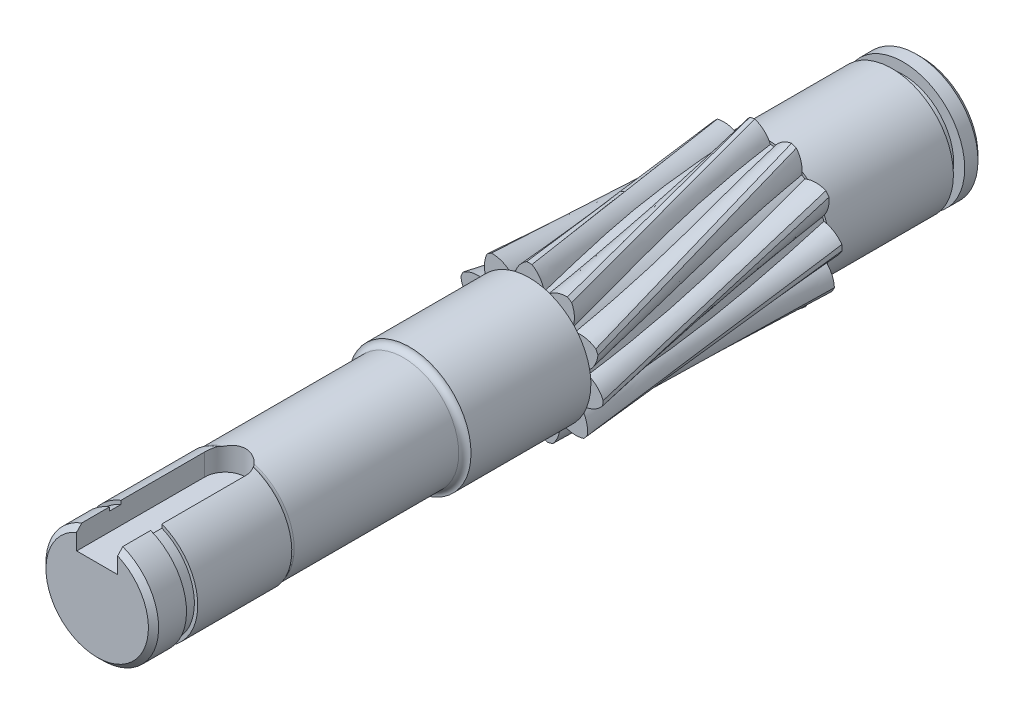
SolidWorks part; units mm, degrees
ref_plane "Plan de face" through (0, 0, 0) normal (0, 0, 1) x (1, 0, 0)
ref_plane "Plan de dessus" through (0, 0, 0) normal (0, 1, 0) x (1, 0, 0)
ref_plane "Plan de droite" through (0, 0, 0) normal (1, 0, 0) x (0, 0, -1)
sketch "Esquisse5" plane through (0, 0, 0) normal (0, 0, 1) x (1, 0, 0)
  circle A0 centre (0, 0) radius 5.75
  dimension "D1" = 11.5
extrude "Extrusion1" add sketch "Esquisse5" against normal blind 23.3
sketch "Esquisse1" plane through (0, 0, 0) normal (0, 0, 1) x (1, 0, 0)
  line L0 (0, 8.3971) -> (0, -8.0185) construction
  line L1 (-0.25, 7.2457) -> (0, 0) construction
  line L2 (0, 0) -> (0.25, 7.2457) construction
  line L3 (1.45, 5.5642) -> (0, 0) construction
  line L4 (0, 0) -> (-1.45, 5.5642) construction
  circle A0 centre (0, 0) radius 5.75 construction
  circle A1 centre (0, 0) radius 7.25 construction
  arc A2 (-0.25, 7.2457) -> (0.25, 7.2457) centre (0, 0) cw
  arc A3 (-1.45, 5.5642) -> (1.45, 5.5642) centre (0, 0) cw
  arc A4 (-1.45, 5.5642) -> (-0.25, 7.2457) centre (1.1069, 5.0084) cw
  arc A5 (1.45, 5.5642) -> (0.25, 7.2457) centre (-1.1069, 5.0084) ccw
  circle A6 centre (0, 0) radius 5.75 construction
  dimension "D1" = 0.5
  dimension "D2" = 14.5
  dimension "D4" = 1.5
  dimension "D5" = 2.6166
  dimension "D3" = 2.9
  dimension "angle1" = 3.952
  dimension "angle2" = 29.212
sketch "Esquisse6" plane through (0, 0, -23.3) normal (0, 0, -1) x (-1, 0, 0)
  line L0 (0, 0) -> (6.6208, 6.6208) construction
  line L1 (0, 8.3971) -> (0, -8.0185) construction
  line L2 (0, 0) -> (4.9467, 5.3003) construction
  line L3 (0, 0) -> (5.3003, 4.9467) construction
  line L4 (0, 0) -> (2.9092, 4.9598) construction
  line L5 (0, 0) -> (4.9598, 2.9092) construction
  arc A0 (5.3003, 4.9467) -> (4.9467, 5.3003) centre (0, 0) ccw
  arc A1 (0.25, 7.2457) -> (-0.25, 7.2457) centre (0, 0) ccw construction
  circle A2 centre (0, 0) radius 7.25 construction
  arc A3 (2.9092, 4.9598) -> (4.9467, 5.3003) centre (4.3242, 2.7588) cw
  arc A4 (-0.25, 7.2457) -> (-1.45, 5.5642) centre (1.1069, 5.0084) ccw construction
  arc A5 (4.9598, 2.9092) -> (5.3003, 4.9467) centre (2.7588, 4.3242) ccw
  arc A6 (4.9598, 2.9092) -> (2.9092, 4.9598) centre (0, 0) ccw
  circle A7 centre (0, 0) radius 5.75 construction
  dimension "D1" = 45
loft "Lissage3" add profiles "Esquisse1", "Esquisse6"
pattern_circular "Répétition circulaire2" count 11 over 360 about axis through (0, 0, -23.3) along (0, 0, 1) of "Lissage3" reverse direction yes
sketch "Esquisse7" plane through (0, 0, 0) normal (1, 0, 0) x (0, 0, -1)
  line L0 (-54.4054, 0) -> (40.026, 0) construction
  line L1 (23.3, 0) -> (0, 0) construction
  line L2 (-42.2, 0) -> (-42.2, 5)
  line L3 (23.3, 4.7066) -> (23.3, 6.7015) construction
  line L4 (38.3, 5.5) -> (38.3, 0)
  line L5 (37.8, 6) -> (36.5, 6)
  line L6 (36.5, 6) -> (36.5, 4.92)
  line L7 (36.5, 4.92) -> (35.4, 4.92)
  line L8 (35.4, 4.92) -> (35.4, 6)
  line L9 (35.4, 6) -> (23.3, 6)
  line L10 (23.3, 2.1737) -> (23.3, 4.142) construction
  line L11 (38.3, 5.5) -> (37.8, 6)
  line L12 (0, 6) -> (-11.7, 6)
  line L13 (0, 5.9603) -> (0, 3.8969) construction
  line L14 (-12.3, 5.4) -> (-28.3683, 5.4)
  line L15 (-28.7, 5.5) -> (-37.88, 5.5)
  line L16 (-37.88, 5.5) -> (-37.88, 5.17)
  line L17 (-37.88, 5.17) -> (-38.98, 5.17)
  line L18 (-38.98, 5.17) -> (-38.98, 5.5)
  line L19 (-38.98, 5.5) -> (-41.7, 5.5)
  line L20 (-41.7, 5.5) -> (-42.2, 5)
  line L21 (-42.2, 0) -> (0, 0)
  line L22 (0, 0) -> (0, 6)
  line L23 (23.3, 6) -> (23.3, 0)
  line L24 (23.3, 0) -> (38.3, 0)
  arc A0 (-11.7, 6) -> (-12.3, 5.4) centre (-12.3, 6) cw
  arc A1 (-28.3683, 5.4) -> (-28.7, 5.5) centre (-28.3683, 6) cw
  point P8 (38.3, 6)
  point P35 (-42.2, 5.5)
  dimension "D8" = 0.6
  dimension "D1" = 80.5
  dimension "D2" = 15
  dimension "D3" = 12
  dimension "D4" = 1.8
  dimension "D5" = 1.1
  dimension "D6" = 9.84
  dimension "D10" = 0.5
  dimension "D7" = 11.7
  dimension "D9" = 11
  dimension "D11" = 4.32
  dimension "D12" = 1.1
  dimension "D13" = 10.34
  dimension "D16" = 0.5
  dimension "D14" = 13.5
revolve "Révolution1" add sketch "Esquisse7" angle 360 about L0
ref_plane "Plan2" through (0, 5.5, 33.29) normal (0, 1, 0) x (-1, 0, 0)
sketch "Esquisse8" plane through (0, 5.5, 33.29) normal (0, 1, 0) x (-1, 0, 0)
  line L0 (-2, 8.91) -> (-2, -3.59)
  line L1 (5, 8.91) -> (-5, 8.91) construction
  line L2 (2, -3.59) -> (2, 8.91)
  line L3 (2, 8.91) -> (-2, 8.91)
  line L4 (0, 10.2561) -> (0, -4.5403) construction
  line L5 (0, 21.1154) -> (0, -73.316) construction
  arc A0 (-2, -3.59) -> (2, -3.59) centre (0, -3.59) ccw
  dimension "D1" = 4
  dimension "D2" = 12.5
extrude "Enlèv. mat.-Extru.1" cut sketch "Esquisse8" against normal blind 2.5
